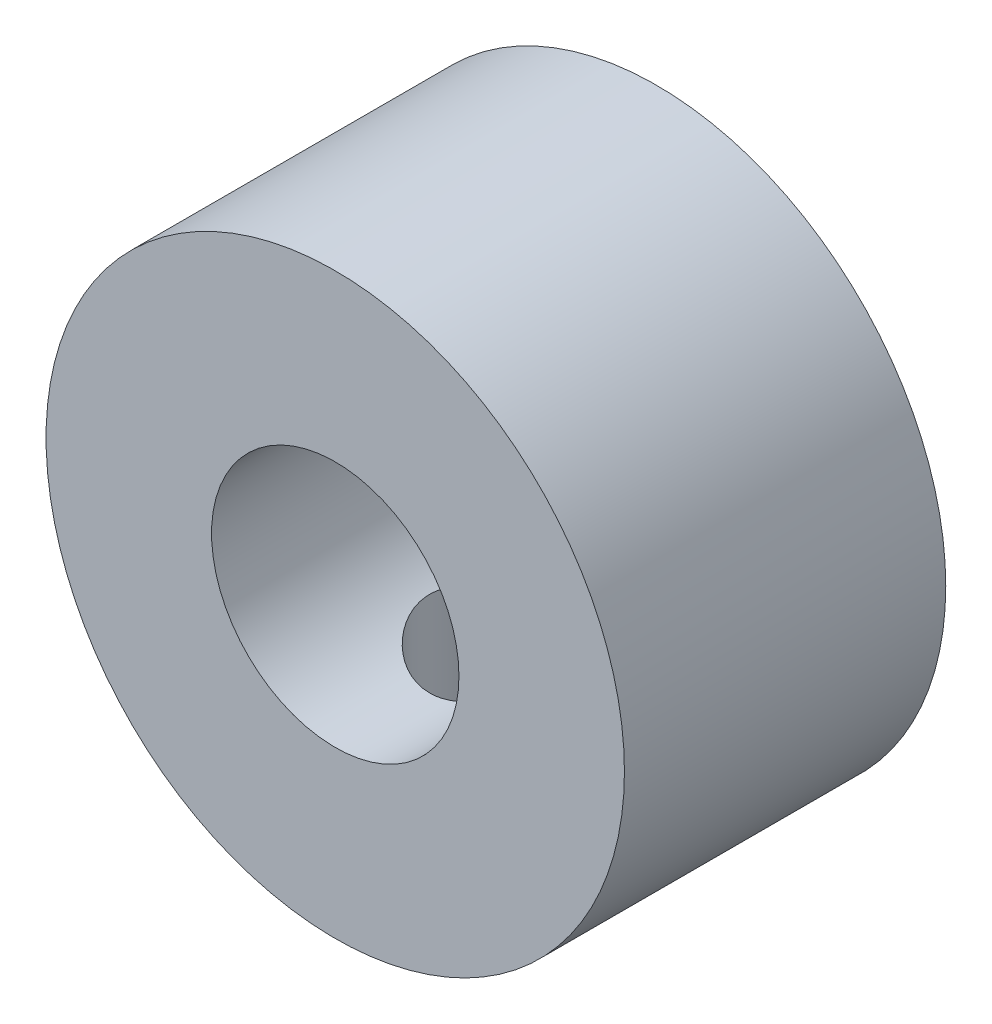
SolidWorks part; units mm, degrees
ref_plane "前视基准面" through (0, 0, 0) normal (0, 0, 1) x (1, 0, 0)
ref_plane "上视基准面" through (0, 0, 0) normal (0, 1, 0) x (1, 0, 0)
ref_plane "右视基准面" through (0, 0, 0) normal (1, 0, 0) x (0, 0, -1)
other "Configuration Table"
sketch "草图1" plane through (0, 0, 0) normal (0, 0, 1) x (1, 0, 0)
  circle A0 centre (0, 0) radius 3.6
  circle A1 centre (0, 0) radius 1.54
  dimension "D1" = 7.2
  dimension "D2" = 3.08
extrude "凸台-拉伸1" add sketch "草图1" along normal blind 4
sketch "草图2" plane through (0, 0, 0) normal (0, 1, 0) x (1, 0, 0)
  line L0 (0, -4) -> (0, 0) construction
  line L1 (-3.6, -4) -> (3.6, -4) construction
  circle A0 centre (0, -2) radius 0.825
  dimension "D1" = 1.65
extrude "切除-拉伸1" cut sketch "草图2" against normal up to next
